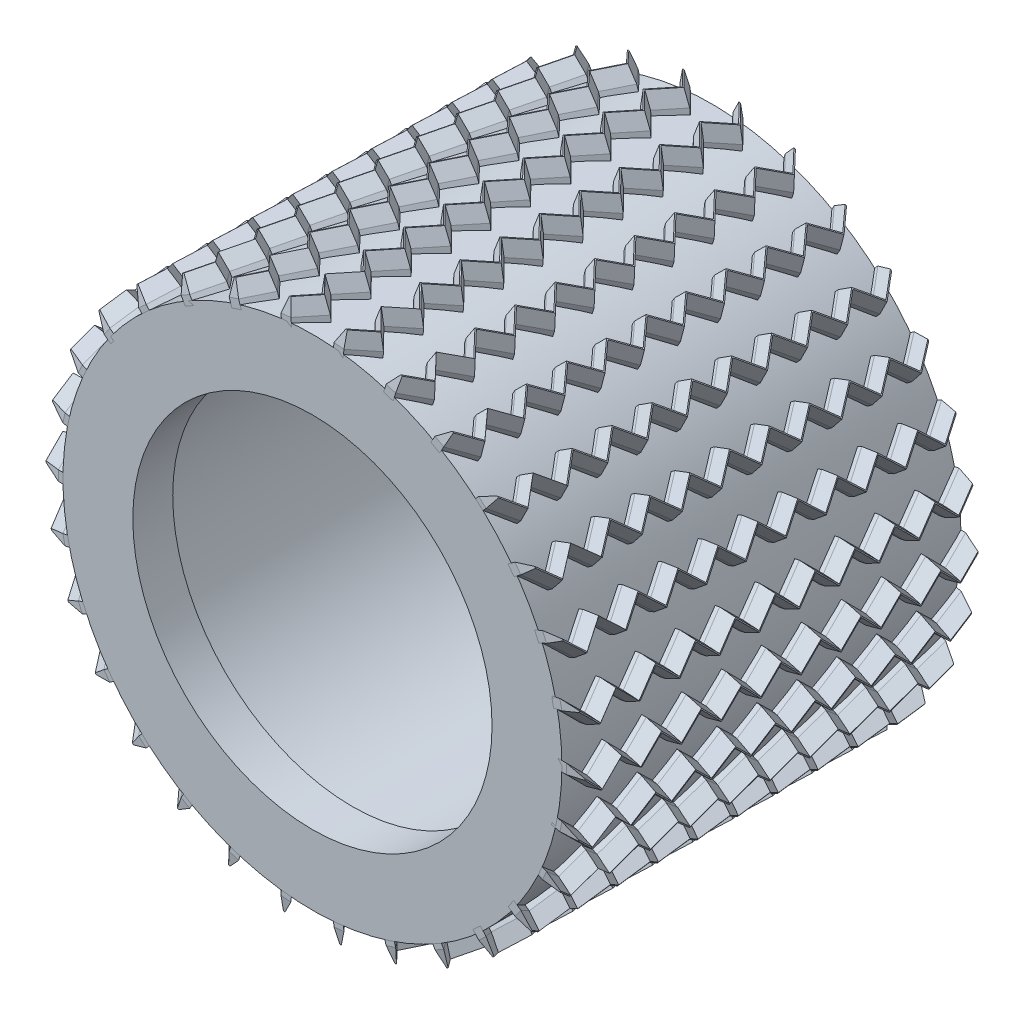
SolidWorks part; units mm, degrees
material "POLIURETANO (11671)"
ref_plane "Alzado" through (0, 0, 0) normal (0, 0, 1) x (1, 0, 0)
ref_plane "Planta" through (0, 0, 0) normal (0, 1, 0) x (1, 0, 0)
ref_plane "Vista lateral" through (0, 0, 0) normal (1, 0, 0) x (0, 0, -1)
sketch "Croquis1" plane through (0, 0, 0) normal (0, 0, 1) x (1, 0, 0)
  circle A0 centre (0, 0) radius 125
  circle A1 centre (0, 0) radius 100
  dimension "D1" = 250
  dimension "D2" = 200
extrude "Saliente-Extruir1" add sketch "Croquis1" along normal mid plane 160
sketch "Croquis2" plane through (0, 0, 0) normal (0, 0, 1) x (1, 0, 0)
  line L0 (0, 0) -> (-100, 0) construction
  circle A0 centre (0, 0) radius 100 construction
  circle A1 centre (0, 0) radius 90
  circle A2 centre (0, 0) radius 125
  dimension "D1" = 180
ref_plane "Plano1" through (125, 0, 0) normal (1, 0, 0) x (0, 0, -1)
sketch "Croquis5" plane through (0, 0, 80) normal (0, 0, 1) x (1, 0, 0)
  circle A0 centre (0, 0) radius 90 construction
  circle A1 centre (0, 0) radius 90
  circle A2 centre (0, 0) radius 125 construction
  circle A3 centre (0, 0) radius 125
extrude "Saliente-Extruir2" add sketch "Croquis5" along normal blind 20
mirror "Simetría1" about plane through (0, 0, 0) normal (0, 0, 1) of "Saliente-Extruir2"
sketch "Croquis6" plane through (125, 0, 0) normal (1, 0, 0) x (0, 0, -1)
  line L0 (-100, -2.5) -> (-100, 2.5)
  line L1 (0, -2.5) -> (-10.2178, -12.6321)
  line L2 (-100, 125) -> (-100, -125) construction
  line L3 (-100, 2.5) -> (0, 2.5) construction
  line L4 (0, 125) -> (0, -125) construction
  line L5 (0, 2.5) -> (-10.2178, -7.6321)
  line L6 (-10.2178, -7.6321) -> (-20.0137, 2.2468)
  line L7 (-20.0137, 2.2468) -> (-30.0559, -7.711)
  line L9 (-30.0559, -7.711) -> (-40.0137, 2.3312)
  line L10 (-40.0137, 2.3312) -> (-50.0559, -7.6266)
  line L11 (-50.0559, -7.6266) -> (-60.0137, 2.4156)
  line L12 (-60.0137, 2.4156) -> (-70.4265, -7.9097)
  line L13 (-70.4265, -7.9097) -> (-80.0137, 1.7587)
  line L14 (-80.0137, 1.7587) -> (-89.7208, -7.8669)
  line L15 (-89.7208, -7.8669) -> (-100, 2.5)
  line L16 (-10.2178, -12.6321) -> (-20.0137, -2.7532)
  line L17 (-20.0137, -2.7532) -> (-30.0559, -12.711)
  line L18 (-30.0559, -12.711) -> (-40.0137, -2.6688)
  line L19 (-40.0137, -2.6688) -> (-50.0559, -12.6266)
  line L20 (-50.0559, -12.6266) -> (-60.0137, -2.5844)
  line L21 (-60.0137, -2.5844) -> (-70.0559, -12.5422)
  line L22 (-70.0559, -12.5422) -> (-80.0137, -2.5)
  line L23 (-80.0137, -2.5) -> (-90.0915, -12.4931)
  line L24 (-90.0915, -12.4931) -> (-100, -2.5)
  line L26 (100, -2.5) -> (89.7891, -12.6252)
  line L27 (0, 2.5) -> (100, 2.5) construction
  line L28 (100, 2.5) -> (89.7891, -7.6252)
  line L29 (89.7891, -7.6252) -> (80, 2.2468)
  line L30 (80, 2.2468) -> (69.9579, -7.711)
  line L31 (100, -2.5) -> (100, 2.5)
  line L32 (69.9579, -7.711) -> (60, 2.3312)
  line L33 (60, 2.3312) -> (49.9579, -7.6266)
  line L34 (49.9579, -7.6266) -> (40, 2.4156)
  line L35 (40, 2.4156) -> (29.9579, -7.5422)
  line L36 (29.9579, -7.5422) -> (20, 2.5)
  line L37 (20, 2.5) -> (9.9153, -7.5)
  line L38 (9.9153, -7.5) -> (0, 2.5)
  line L39 (89.7891, -12.6252) -> (80, -2.7532)
  line L40 (80, -2.7532) -> (69.9579, -12.711)
  line L41 (69.9579, -12.711) -> (60, -2.6688)
  line L42 (60, -2.6688) -> (49.9579, -12.6266)
  line L43 (49.9579, -12.6266) -> (40, -2.5844)
  line L44 (40, -2.5844) -> (29.9579, -12.5422)
  line L45 (29.9579, -12.5422) -> (20, -2.5)
  line L46 (20, -2.5) -> (9.9153, -12.5)
  line L47 (9.9153, -12.5) -> (0, -2.5)
  point P5 (-100, 0)
  point P10 (0, 0)
  point P32 (0, 0)
  point P33 (0, 0)
  point P36 (100.7284, 0)
  point P55 (100, 0)
  dimension "D1" = 5
  dimension "D3" = 20
  dimension "D4" = 20
  dimension "D5" = 20
  dimension "D6" = 89.998
  dimension "D7" = 5
  dimension "D8" = 20
  dimension "D9" = 20
  dimension "D10" = 20
  dimension "D11" = 20
  dimension "D12" = 20
  dimension "D13" = 20
  dimension "D14" = 20
  dimension "D15" = 20
  dimension "D16" = 89.998
  dimension "D17" = 89.998
  dimension "D19" = 20
  dimension "D20" = 20
  dimension "D21" = 44.756
  dimension "D22" = 20
  dimension "D23" = 89.998
extrude "Saliente-Extruir3" add sketch "Croquis6" along normal blind 12 from offset 2 separate body offset against normal yes
chamfer "Chaflán1" distance 1.5 angle 79 42 edges at (135, 0, 100) (135, -2.6835, 94.8604) (135, -3.0541, 84.8673) (135, -3.0755, 75.2201) (135, -2.7471, 65.2201) (135, -2.6055, 55.0348) (135, -2.6477, 45.0348) (135, -2.6899, 35.0348) (135, -2.7321, 25.0348) (135, -2.6926, 15.1158) (135, -2.566, 5.1089) (135, -2.5, -4.9577) (135, -2.5, -14.9577) (135, -2.5211, -24.9789) (135, -2.5633, -34.9789) (135, -2.6055, -44.9789) (135, -2.6477, -54.9789) (135, -2.6899, -64.9789) (135, -2.7321, -74.9789) (135, -2.6892, -84.8945) (135, -2.5626, -94.8945) (135, 0, -100) (135, -7.5626, -94.8945) (135, -7.6892, -84.8945) (135, -7.7321, -74.9789) (135, -7.6899, -64.9789) (135, -7.6477, -54.9789) (135, -7.6055, -44.9789) (135, -7.5633, -34.9789) (135, -7.5211, -24.9789) (135, -7.5, -14.9577) (135, -7.5, -4.9577) (135, -7.566, 5.1089) (135, -7.6926, 15.1158) (135, -7.7321, 25.0348) (135, -7.6899, 35.0348) (135, -7.6477, 45.0348) (135, -7.6055, 55.0348) (135, -7.5633, 65.0348) (135, -7.5211, 75.0348) (135, -7.4966, 85.0526) (135, -7.4966, 95.0457)
pattern_circular "MatrizC7" count 30 over 360 about axis through (0, 0, 0) along (0, 0, 1) of bodies 104
